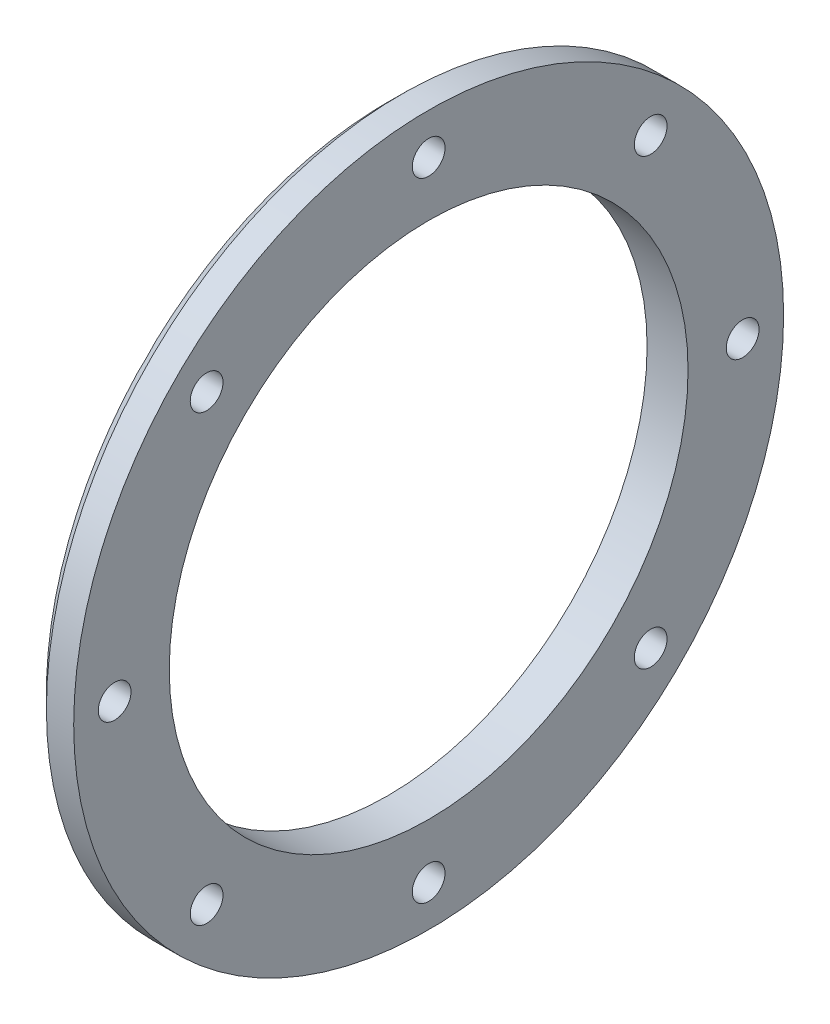
SolidWorks part; units mm, degrees
material "ПК/АБС"
ref_plane "Спереди" through (0, 0, 0) normal (0, 0, 1) x (1, 0, 0)
ref_plane "Сверху" through (0, 0, 0) normal (0, 1, 0) x (1, 0, 0)
ref_plane "Справа" through (0, 0, 0) normal (1, 0, 0) x (0, 0, -1)
sketch "Эскиз1" plane through (0, 0, 0) normal (0, 0, 1) x (1, 0, 0)
  line L5 (0, 19) -> (0, 25)
  line L6 (0, 25) -> (1, 26)
  line L7 (1, 26) -> (3, 26)
  line L8 (3, 26) -> (3, 19)
  line L9 (3, 19) -> (0, 19)
  line L10 (0, 0) -> (0, 19) construction
  line L11 (0, 0) -> (16163.9124, 0) construction
  point P7 (1.5, 19)
  dimension "D1" = 52
  dimension "D2" = 3
  dimension "D3" = 1
  dimension "D4" = 45
  dimension "D5" = 38
revolve "Повернуть1" add sketch "Эскиз1" angle 360 about L11
hole_wizard "Зенковка для винта с потайной головкой M21" positions "Эскиз2" profile "Эскиз3" countersink size "M2" standard "HASCO Metric" end condition through all
sketch "Эскиз2" plane through (0, 0, 0) normal (-1, 0, 0) x (0, 0, 1)
  line L0 (0, 0) -> (0, 25) construction
  line L2 (0, 0) -> (17.6777, 17.6777) construction
  circle A0 centre (0, 0) radius 25 construction
  circle A1 centre (0, 0) radius 23
  point P0 (16.2635, 16.2635)
  dimension "D2" = 46
  dimension "D1" = 45
sketch "Эскиз3" plane through (0, 16.2635, 16.2635) normal (0, 1, 0) x (0, 0, 1)
  line L0 (0, 0) -> (0, 3)
  line L1 (0, 3) -> (1.2, 3)
  line L2 (1.2, 3) -> (1.2, 1)
  line L3 (1.2, 1) -> (2.2, 0)
  line L5 (2.2, 0) -> (0, 0)
  line L6 (-1.2, 1) -> (-2.2, 0) construction
  line L11 (0, -6.35) -> (0, 107.95) construction
  dimension "Диаметр сквозного отверстия" = 2.4
  dimension "Глубина сквозного отверстия" = 3
  dimension "Диаметр передней зенковки" = 4.4
  dimension "Угол передней зенковки" = 90
pattern_circular "Круговой массив1" count 8 over 360 about axis through (0, 0, 0) along (-1, 0, 0) of "Зенковка для винта с потайной головкой M21" reverse direction yes
